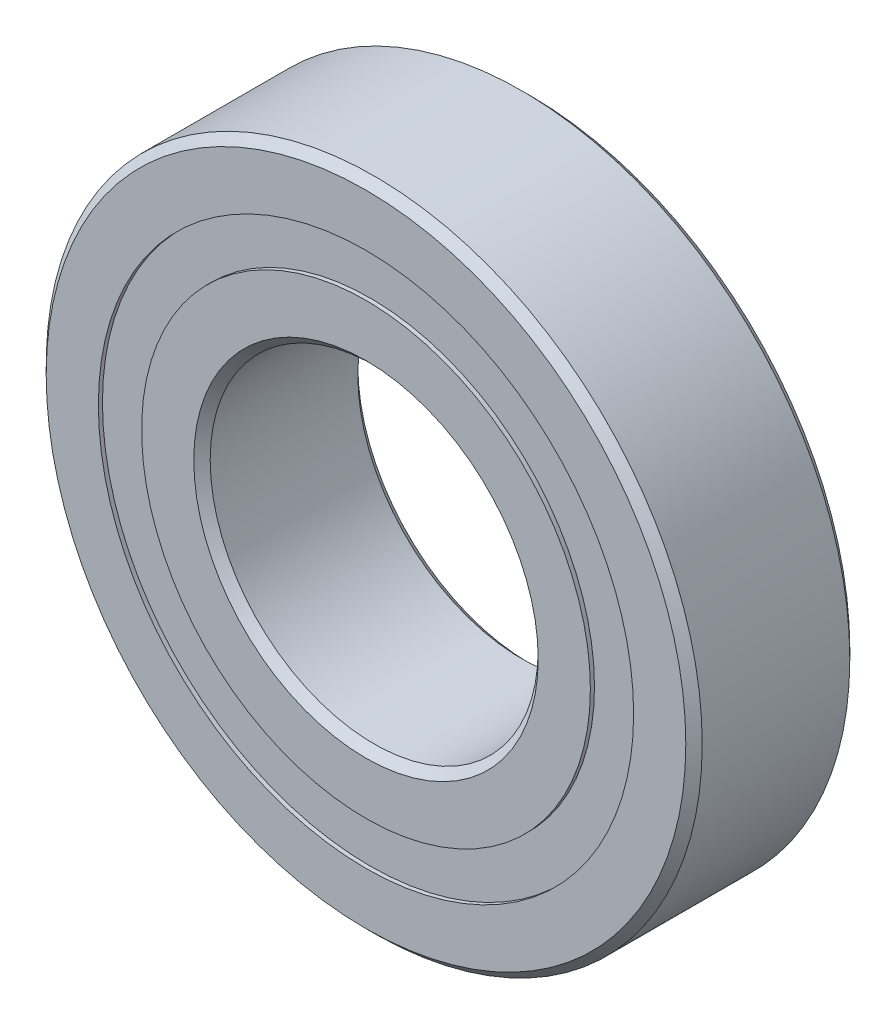
SolidWorks part; units mm, degrees
note: '?' marks a value the reader was unsure of.
ref_plane "Front Plane" through (0, 0, 0) normal (0, 0, 1) x (1, 0, 0)
ref_plane "Top Plane" through (0, 0, 0) normal (0, 1, 0) x (1, 0, 0)
ref_plane "Right Plane" through (0, 0, 0) normal (1, 0, 0) x (0, 0, -1)
sketch "Sketch1" plane through (0, 0, 0) normal (1, 0, 0) x (0, 0, -1)
  line L0 (-6.35, 0) -> (6.35, 0) construction
  line L1 (0, 25.4) -> (0, -25.4) construction
  line L2 (5.715, 25.4) -> (-5.715, 25.4)
  line L3 (-5.715, 25.4) -> (-6.35, 24.765)
  line L4 (-6.35, 24.765) -> (-6.35, 20.7247)
  line L5 (-6.35, 20.7247) -> (-2.8222, 20.7247)
  line L6 (6.35, 20.7247) -> (2.8222, 20.7247)
  line L7 (6.35, 24.765) -> (6.35, 20.7247)
  line L8 (5.715, 25.4) -> (6.35, 24.765)
  line L9 (0, 25.4) -> (0, 19.05) construction
  line L10 (0, 19.05) -> (0, 12.7) construction
  arc A0 (-2.8222, 20.7247) -> (2.8222, 20.7247) centre (0, 19.05) cw
  point P14 (0, 12.7)
  dimension "Width" = 12.7
  dimension "OD" = 50.8
  dimension "D1" = 45
  dimension "D2" = 0.635
  dimension "Shaft Dia" = 25.4
  dimension "D3" = 5.6444
  dimension "D4" = 1.6747
revolve "Revolve1" add sketch "Sketch1" angle 360 about L0
sketch "Sketch3" plane through (0, 0, 0) normal (1, 0, 0) x (0, 0, -1)
  line L0 (-6.35, 17.3753) -> (-2.8222, 17.3753)
  line L1 (0, 25.4) -> (0, -25.4) construction
  line L2 (-6.35, 24.765) -> (-6.35, 20.7247) construction
  line L3 (-6.35, 17.3753) -> (-6.35, 13.335)
  line L4 (-5.715, 25.4) -> (-6.35, 24.765) construction
  line L5 (-6.35, 13.335) -> (-5.715, 12.7)
  line L6 (-5.715, 12.7) -> (5.715, 12.7)
  line L7 (5.715, 25.4) -> (5.715, -25.4) construction
  line L8 (5.715, 12.7) -> (6.35, 13.335)
  line L9 (6.35, -24.765) -> (6.35, 24.765) construction
  line L10 (6.35, 13.335) -> (6.35, 17.3753)
  line L11 (6.35, 17.3753) -> (2.8222, 17.3753)
  line L13 (5.715, 25.4) -> (6.35, 24.765) construction
  arc A0 (2.8222, 20.7247) -> (-2.8222, 20.7247) centre (0, 19.05) ccw construction
  arc A1 (2.8222, 17.3753) -> (-2.8222, 17.3753) centre (0, 19.05) cw
revolve "Revolve3" add sketch "Sketch3" angle 360 about L0
sketch "Sketch4" plane through (0, 0, 0) normal (1, 0, 0) x (0, 0, -1)
  line L0 (-3.2817, 19.05) -> (3.2817, 19.05)
  arc A2 (-3.2817, 19.05) -> (3.2817, 19.05) centre (0, 19.05) cw
  arc A3 (2.8222, 20.7247) -> (-2.8222, 20.7247) centre (0, 19.05) ccw construction
revolve "Revolve4" add sketch "Sketch4" angle 360 about L0
ref_axis "Axis1" through (0, 0, -6.35) along (0, 0, 1)?
pattern_circular "CirPattern1" count 12 every 30 about axis through (0, 0, 0) along (0, 0, 1) of bodies 104
sketch "Sketch5" plane through (0, 0, 0) normal (1, 0, 0) x (0, 0, -1)
  line L0 (-6.35, 20.7247) -> (-2.8222, 20.7247) construction
  line L1 (-6.0325, 20.7247) -> (-3.2817, 20.7247)
  line L2 (-6.0325, 20.7247) -> (-6.0325, 17.3753)
  line L3 (-6.0325, 17.3753) -> (-3.2817, 17.3753)
  line L4 (-3.2817, 20.7247) -> (-3.2817, 17.3753)
  line L5 (-6.35, 17.3753) -> (-2.8222, 17.3753) construction
  line L6 (6.35, 20.7247) -> (2.8222, 20.7247) construction
  line L7 (6.0325, 20.7247) -> (3.2817, 20.7247)
  line L8 (6.0325, 20.7247) -> (6.0325, 17.3753)
  line L9 (6.0325, 17.3753) -> (3.2817, 17.3753)
  line L10 (3.2817, 20.7247) -> (3.2817, 17.3753)
  line L11 (6.35, 17.3753) -> (2.8222, 17.3753) construction
  line L12 (-5.715, 25.4) -> (-6.35, 24.765) construction
  point P18 (-6.0325, 25.0825)
revolve "Revolve5" add sketch "Sketch5" angle 360 about L0
equation "\"D2@Sketch1\" = \"Width@Sketch1\"*.05"
equation "\"D3@Sketch1\" = \"Width@Sketch1\"/2.25"
equation "\"D4@Sketch1\" = (((\"OD@Sketch1\"-\"Width@Sketch1\")/2)/3.25)/3.5"
equation "\"D2@CirPattern1\" = 360/\"Balls@CirPattern1\""
